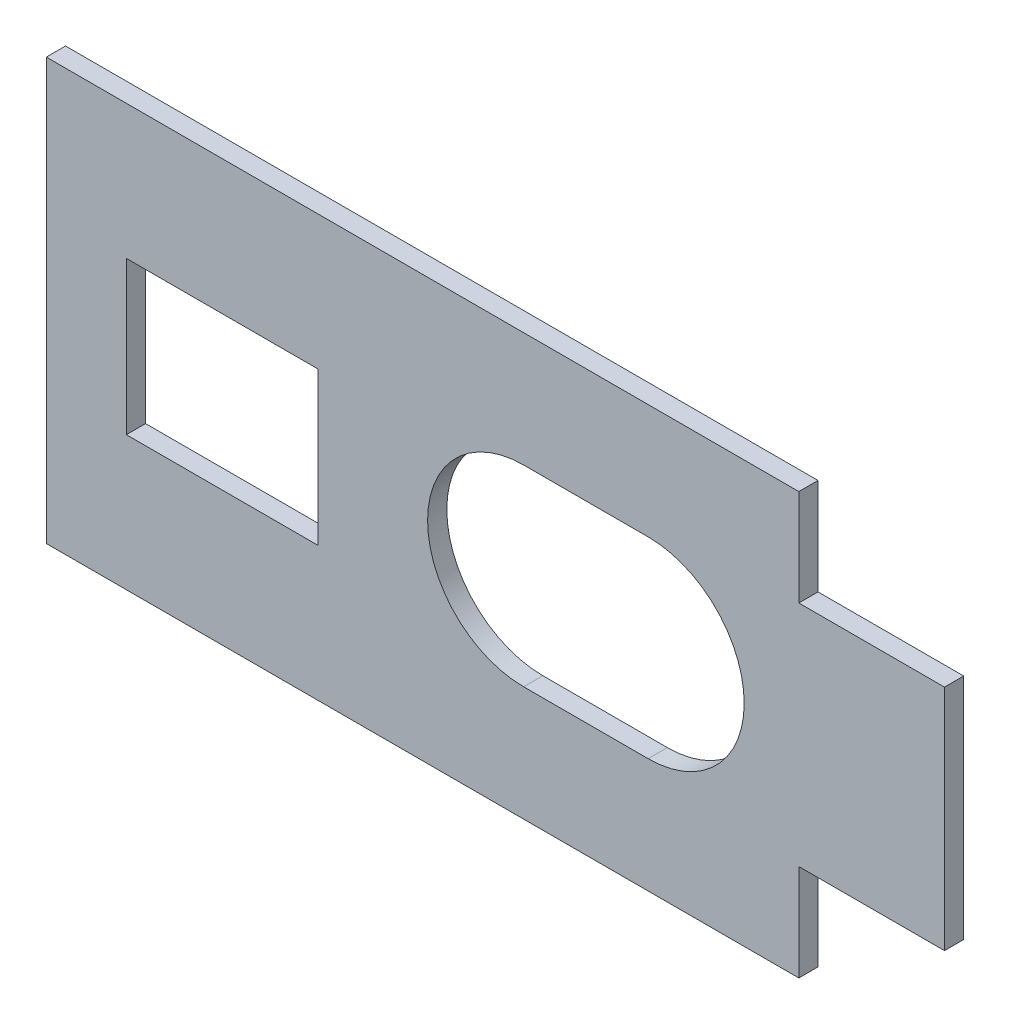
SolidWorks part; units mm, degrees
ref_plane "Front Plane" through (0, 0, 0) normal (0, 0, 1) x (1, 0, 0)
ref_plane "Top Plane" through (0, 0, 0) normal (0, 1, 0) x (1, 0, 0)
ref_plane "Right Plane" through (0, 0, 0) normal (1, 0, 0) x (0, 0, -1)
sketch "Sketch1" plane through (0, 0, 0.762) normal (0, 0, 1) x (1, 0, 0)
  line L0 (-10.7161, -30.2624) -> (-10.7161, -24.7125) construction
  line L1 (-3.6295, -24.7125) -> (-3.6295, -30.2624) construction
  line L2 (-10.7161, -24.5347) -> (-10.7161, -24.7125) construction
  line L3 (-10.7161, -30.2624) -> (-10.7161, -30.4402) construction
  line L4 (10.2389, -20.7184) -> (-19.6442, -20.7184) construction
  line L12 (-10.7161, -30.2624) -> (-10.7161, -24.7125) construction
  line L13 (-10.7161, -30.4402) -> (1.3108, -30.4402) construction
  line L14 (1.3108, -30.4402) -> (1.3108, -24.5347) construction
  line L15 (1.3108, -24.5347) -> (-10.7161, -24.5347) construction
  line L16 (-10.7161, -30.2624) -> (-10.7161, -24.7125) construction
  line L17 (-3.6295, -24.7125) -> (-3.6295, -30.2624) construction
  line L18 (-10.7161, -24.5347) -> (-10.7161, -24.7125) construction
  line L19 (-10.7161, -30.2624) -> (-10.7161, -30.4402) construction
  line L20 (-10.7161, -30.2624) -> (-10.7161, -24.7125) construction
  line L21 (-10.7161, -30.4402) -> (1.3108, -30.4402) construction
  line L22 (1.3108, -30.4402) -> (1.3108, -24.5347) construction
  line L23 (1.3108, -24.5347) -> (-10.7161, -24.5347) construction
  line L27 (-10.7161, -30.2624) -> (-3.6295, -30.2624) construction
  line L28 (-3.6295, -24.7125) -> (-10.7161, -24.7125) construction
  line L31 (-14.1451, -19.1309) -> (15.7083, -19.1309)
  line L32 (-14.1451, -19.1309) -> (-14.1451, -35.8441)
  line L33 (-14.1451, -35.8441) -> (15.7083, -35.8441)
  line L39 (15.7083, -19.1309) -> (15.7083, -22.9599)
  line L45 (21.4868, -22.9599) -> (21.4868, -32.015)
  line L46 (21.4868, -32.015) -> (15.7083, -32.015)
  line L47 (15.7083, -32.015) -> (15.7083, -35.8441)
  line L49 (9.7309, -27.4875) -> (4.7906, -27.4875) construction
  line L54 (9.7309, -31.2975) -> (4.7906, -31.2975)
  line L55 (9.7309, -23.6775) -> (4.7906, -23.6775)
  line L56 (-3.6295, -30.2624) -> (1.3108, -30.2624) construction
  line L57 (-3.6295, -24.7125) -> (-10.7161, -24.7125) construction
  line L58 (21.4868, -22.9599) -> (20.2168, -22.9599)
  line L59 (20.2168, -22.9599) -> (15.7083, -22.9599)
  line L60 (-10.7161, -30.2624) -> (-3.6295, -30.2624) construction
  line L61 (-10.9701, -24.4585) -> (-3.3755, -24.4585)
  line L62 (-10.9701, -24.4585) -> (-10.9701, -30.5164)
  line L63 (-10.9701, -30.5164) -> (-3.3755, -30.5164)
  line L64 (-3.3755, -24.4585) -> (-3.3755, -30.5164)
  line L84 (22.1218, -22.9599) -> (22.1218, -32.015) construction
  line L85 (22.1218, -32.015) -> (26.6303, -32.015) construction
  line L86 (26.6303, -32.015) -> (26.6303, -22.9599) construction
  line L87 (26.6303, -22.9599) -> (22.1218, -22.9599) construction
  line L88 (22.1218, -22.9599) -> (22.1218, -32.015) construction
  line L89 (22.1218, -32.015) -> (26.6303, -32.015) construction
  line L90 (26.6303, -32.015) -> (26.6303, -22.9599)
  line L91 (26.6303, -22.9599) -> (22.1218, -22.9599) construction
  circle A0 centre (9.7309, -27.4875) radius 1.319 construction
  circle A1 centre (9.7309, -27.4875) radius 1.319 construction
  arc A2 (9.7309, -31.2975) -> (9.7309, -23.6775) centre (9.7309, -27.4875) ccw
  arc A3 (4.7906, -23.6775) -> (4.7906, -31.2975) centre (4.7906, -27.4875) ccw
  point P1 (21.4868, -27.4875)
  point P3 (-14.1451, -27.4875)
  point P28 (7.2607, -27.4875)
  point P38 (20.2168, -22.9599)
  point P45 (-7.1728, -24.4585)
  point P46 (-7.1728, -24.7125)
  point P47 (-3.3755, -27.4875)
  point P48 (-3.6295, -27.4875)
  line M91 (1.3108, -30.4402) -> (-10.7161, -30.4402)
  line M95 (-10.7161, -24.5347) -> (1.3108, -24.5347)
  line M96 (1.3108, -24.5347) -> (1.3108, -30.4402)
  line M97 (10.2389, -20.7184) -> (-19.6442, -20.7184)
  line M101 (-19.6442, -34.2566) -> (10.2389, -34.2566)
  arc M102 (10.2389, -34.2566) -> (12.7789, -31.7166) centre (10.2389, -31.7166) ccw
  line M103 (12.7789, -31.7166) -> (12.7789, -23.2584)
  arc M104 (12.7789, -23.2584) -> (10.2389, -20.7184) centre (10.2389, -23.2584) ccw
  dimension "D3" = 3.81
  dimension "D2" = 1.5875
  dimension "D5" = 1.27
  dimension "D7" = 0.254
  dimension "D8" = 0.254
  dimension "D1" = 3.175
extrude "Boss-Extrude2" add sketch "Sketch1" along normal blind 0.762 contours A2 L32 L33 L47 L46 L45 L58 L59 L39 L31 M103 M102 M101 M97 M104 | A3 L55 A2 L32 L54 L64 L63 L62 L61 M103 M104 M97 M101 M102 M96 M91 M95 | A3 L64 M96 M95 M91 region at (0.7816, -19.5245, 0.762) region at (-1.9531, -21.0198, 0.762) region at (-1.0889, -27.4875, 0.762)
